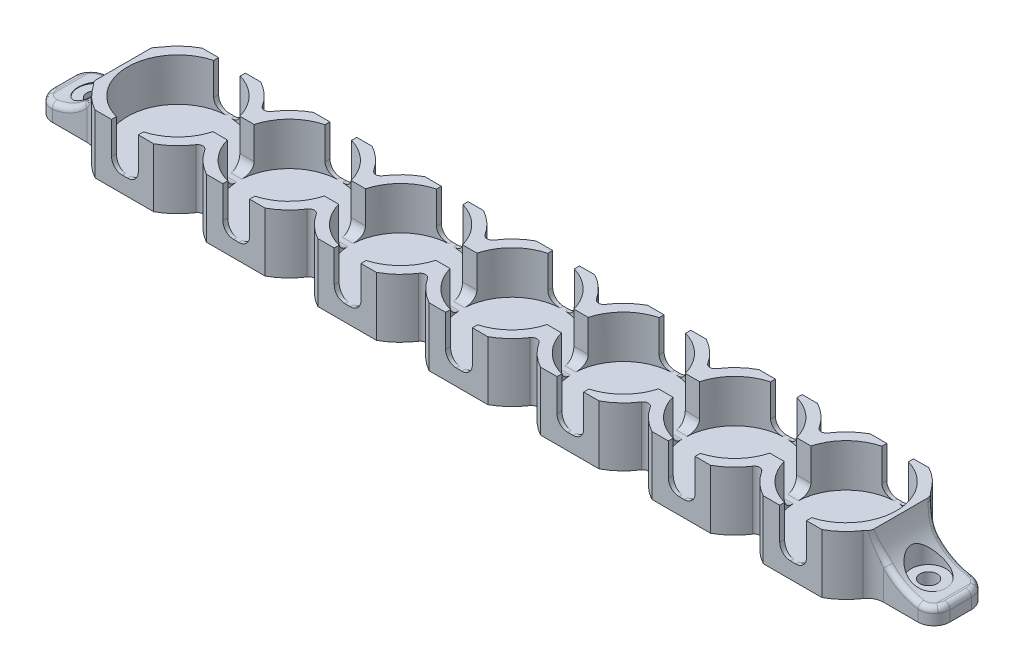
SolidWorks part; units mm, degrees
ref_plane "Front Plane" through (0, 0, 0) normal (0, 0, 1) x (1, 0, 0)
ref_plane "Top Plane" through (0, 0, 0) normal (0, 1, 0) x (1, 0, 0)
ref_plane "Right Plane" through (0, 0, 0) normal (1, 0, 0) x (0, 0, -1)
sketch "Sketch1" plane through (0, 0, 0) normal (0, 1, 0) x (1, 0, 0)
  line L0 (21.4, 5) -> (146.2, 5) construction
  line L1 (0, 10) -> (11.155, 10)
  line L2 (0, 0) -> (0, 10)
  line L3 (0, 0) -> (11.155, 0)
  line L4 (167.6, 0) -> (167.6, 10)
  line L5 (156.445, 10) -> (167.6, 10)
  line L6 (156.445, 0) -> (167.6, 0)
  line L7 (21.4, 5) -> (0, 5) construction
  line L8 (146.2, 5) -> (167.6, 5) construction
  circle A0 centre (21.4, 5) radius 9.4
  circle A1 centre (42.2, 5) radius 9.4
  circle A2 centre (63, 5) radius 9.4
  circle A3 centre (83.8, 5) radius 9.4
  circle A4 centre (104.6, 5) radius 9.4
  circle A5 centre (125.4, 5) radius 9.4
  circle A6 centre (146.2, 5) radius 9.4
  arc A7 (11.155, 10) -> (31.8, 9.669) centre (21.4, 5) cw
  arc A8 (31.8, 9.669) -> (52.6, 9.669) centre (42.2, 5) cw
  arc A9 (52.6, 9.669) -> (73.4, 9.669) centre (63, 5) cw
  arc A10 (73.4, 9.669) -> (94.2, 9.669) centre (83.8, 5) cw
  arc A11 (94.2, 9.669) -> (115, 9.669) centre (104.6, 5) cw
  arc A12 (115, 9.669) -> (135.8, 9.669) centre (125.4, 5) cw
  arc A13 (135.8, 9.669) -> (156.445, 10) centre (146.2, 5) cw
  arc A14 (11.155, 0) -> (31.8, 0.331) centre (21.4, 5) ccw
  arc A15 (31.8, 0.331) -> (52.6, 0.331) centre (42.2, 5) ccw
  arc A16 (52.6, 0.331) -> (73.4, 0.331) centre (63, 5) ccw
  arc A17 (73.4, 0.331) -> (94.2, 0.331) centre (83.8, 5) ccw
  arc A18 (94.2, 0.331) -> (115, 0.331) centre (104.6, 5) ccw
  arc A19 (115, 0.331) -> (135.8, 0.331) centre (125.4, 5) ccw
  arc A20 (135.8, 0.331) -> (156.445, 0) centre (146.2, 5) ccw
  dimension "D1" = 18.8
  dimension "D4" = 2
  dimension "D5" = 12
  dimension "D7" = 2
  dimension "D3" = 10
  dimension "D2" = 7
extrude "Boss-Extrude1" add sketch "Sketch1" along normal blind 11
sketch "Sketch2" plane through (0, 0, 0) normal (0, -1, 0) x (1, 0, 0)
  circle A0 centre (21.4, -5) radius 1.3526
  circle A1 centre (63, -5) radius 1.3525
  circle A2 centre (83.8, -5) radius 1.3525
  circle A3 centre (104.6, -5) radius 1.3525
  circle A4 centre (125.4, -5) radius 1.3526
  circle A5 centre (146.2, -5) radius 9.4 construction
  circle A6 centre (146.2, -5) radius 1.3526
  circle A7 centre (42.2, -5) radius 1.3526
  circle A8 centre (42.2, -5) radius 9.4 construction
  circle A9 centre (146.2, -5) radius 9.4
  circle A10 centre (125.4, -5) radius 9.4
  circle A11 centre (104.6, -5) radius 9.4
  circle A12 centre (83.8, -5) radius 9.4
  circle A13 centre (63, -5) radius 9.4
  circle A14 centre (21.4, -5) radius 9.4 construction
  circle A15 centre (63, -5) radius 9.4 construction
  circle A16 centre (83.8, -5) radius 9.4 construction
  circle A17 centre (104.6, -5) radius 9.4 construction
  circle A18 centre (125.4, -5) radius 9.4 construction
  circle A19 centre (42.2, -5) radius 9.4
  circle A20 centre (21.4, -5) radius 9.4
  dimension "D1" = 2.7051
extrude "Boss-Extrude3" add sketch "Sketch2" against normal blind 3
sketch "Sketch13" plane through (0, 0, 0) normal (0, 0, 1) x (1, 0, 0)
  line L0 (0, 11) -> (0, 0) construction
  line L1 (11.155, 11) -> (0, 11)
  line L2 (11.155, 11) -> (11.155, 3)
  line L4 (11.155, 3) -> (0, 3)
  line L5 (167.6, 11) -> (167.6, 0) construction
  line L6 (0, 11) -> (0, 3)
  line L7 (156.445, 11) -> (167.6, 11)
  line L8 (156.445, 11) -> (156.445, 3)
  line L9 (0, 0) -> (11.155, 0) construction
  line L10 (156.445, 3) -> (167.6, 3)
  line L11 (167.6, 11) -> (167.6, 3)
  line L12 (156.445, 0) -> (167.6, 0) construction
  dimension "D1" = 3
  dimension "D2" = 3
extrude "Cut-Extrude4" cut sketch "Sketch13" against normal through all both and the other way through all
fillet "Fillet2" radius 1 12 edges at (31.8, 5.5, -9.669) (52.6, 5.5, -9.669) (73.4, 5.5, -9.669) (94.2, 5.5, -9.669) (115, 5.5, -9.669) (135.8, 5.5, -9.669) (135.8, 5.5, -0.331) (115, 5.5, -0.331) (94.2, 5.5, -0.331) (73.4, 5.5, -0.331) (52.6, 5.5, -0.331) (31.8, 5.5, -0.331)
fillet "Fillet4" radius 10 2 edges at (11.155, 3, -5) (156.445, 3, -5)
fillet "Fillet5" radius 3 8 edges at (11.155, 5.5, 0) (0, 1.5, 0) (0, 1.5, -10) (11.155, 5.5, -10) (156.445, 5.5, 0) (156.445, 5.5, -10) (167.6, 1.5, 0) (167.6, 1.5, -10)
fillet "Fillet6" radius 1 18 edges at (156.9374, 9.3385, -10.2664) (160.9989, 4.4853, -10) (167.239, 3, -8.4267) (157.4781, 8.1858, 0.0817) (160.9989, 4.4853, 0) (167.239, 3, -1.5733) (10.6626, 9.3385, 0.2664) (6.6011, 4.4853, 0) (0.361, 3, -1.5733) (10.1219, 8.1858, -10.0817) (6.6011, 4.4853, -10) (0.361, 3, -8.4267) (167.6, 3, -5) (0, 3, -5) (165.3504, 3.0399, -9.9046) (165.5574, 3.0235, -0.1569) (2.2496, 3.0399, -0.0954) (2.0426, 3.0235, -9.8431)
sketch "Sketch14" plane through (0, 0, 0) normal (0, -1, 0) x (1, 0, 0)
  line L0 (0, -7) -> (0, -3) construction
  line L1 (6, -5) -> (0, -5) construction
  line L4 (161.6, -5) -> (167.6, -5) construction
  line L5 (167.6, -3) -> (167.6, -7) construction
  circle A0 centre (6, -5) radius 1.6
  circle A1 centre (161.6, -5) radius 1.6
  point P9 (167.6, -5)
  point P11 (0, -5)
  dimension "D1" = 3.2
  dimension "D2" = 6
extrude "Cut-Extrude5" cut sketch "Sketch14" against normal through all
sketch "Sketch16" plane through (0, 11, 0) normal (0, -1, 0) x (1, 0, 0)
  circle A1 centre (6, -5) radius 3.25
  circle A2 centre (161.6, -5) radius 3.25
  circle A3 centre (161.6, -5) radius 1.6 construction
  circle A4 centre (6, -5) radius 1.6 construction
  dimension "D1" = 6.5
extrude "Cut-Extrude7" cut sketch "Sketch16" along normal offset from surface (8 mm away) 3 up to face at (161.6, 0, -6.6)
sketch "Sketch17" plane through (0, 0, 0) normal (0, 0, 1) x (1, 0, 0)
  line L0 (30.8, 3) -> (12, 3) construction
  line L1 (19, 18) -> (24, 18)
  line L2 (19, 18) -> (19, 3)
  line L3 (19, 3) -> (24, 3)
  line L4 (24, 18) -> (24, 3)
  line L5 (39.8, 18) -> (44.8, 18)
  line L6 (39.8, 18) -> (39.8, 3)
  line L7 (39.8, 3) -> (44.8, 3)
  line L8 (44.8, 18) -> (44.8, 3)
  line L9 (60.6, 18) -> (65.6, 18)
  line L10 (60.6, 18) -> (60.6, 3)
  line L11 (60.6, 3) -> (65.6, 3)
  line L12 (65.6, 18) -> (65.6, 3)
  line L13 (81.4, 18) -> (86.4, 18)
  line L14 (81.4, 18) -> (81.4, 3)
  line L15 (81.4, 3) -> (86.4, 3)
  line L16 (86.4, 18) -> (86.4, 3)
  line L17 (102.2, 18) -> (107.2, 18)
  line L18 (102.2, 18) -> (102.2, 3)
  line L19 (102.2, 3) -> (107.2, 3)
  line L20 (107.2, 18) -> (107.2, 3)
  line L21 (123, 18) -> (128, 18)
  line L22 (123, 18) -> (123, 3)
  line L23 (123, 3) -> (128, 3)
  line L24 (128, 18) -> (128, 3)
  line L25 (143.8, 18) -> (148.8, 18)
  line L26 (143.8, 18) -> (143.8, 3)
  line L27 (143.8, 3) -> (148.8, 3)
  line L28 (148.8, 18) -> (148.8, 3)
  line L31 (155.6, 3) -> (136.8, 3) construction
  point P6 (21.5, 3)
  point P7 (42.3, 3)
  dimension "D1" = 21.5
  dimension "D2" = 5
  dimension "D3" = 15
  dimension "D5" = 20.8
  dimension "D4" = 7
extrude "Cut-Extrude8" cut sketch "Sketch17" against normal through all both and the other way through all
sketch "Sketch18" plane through (0, 0, 0) normal (1, 0, 0) x (0, 0, -1)
  line L0 (5, 3) -> (5, 0) construction
  line L1 (2.5, 18) -> (7.5, 18)
  line L2 (2.5, 18) -> (2.5, 3)
  line L3 (2.5, 3) -> (7.5, 3)
  line L4 (7.5, 18) -> (7.5, 3)
  line L5 (7, 0) -> (3, 0) construction
  line L6 (14.0885, 3) -> (-4.0885, 3) construction
  dimension "D1" = 5
  dimension "D2" = 15
extrude "Cut-Extrude9" cut sketch "Sketch18" along normal offset from surface (124.6 mm away) 21.5 from offset 21.5 up to face at (167.6, 1, -5)
fillet "Fillet7" radius 2 40 edges at (143.8, 3, -15.1165) (148.8, 3, -15.0664) (135.8, 3, -2.5) (135.8, 3, -7.5) (128, 3, -15.0664) (123, 3, -15.1165) (115, 3, -2.5) (115, 3, -7.5) (107.2, 3, -15.0664) (102.2, 3, -15.1165) (94.2, 3, -7.5) (94.2, 3, -2.5) (86.4, 3, -15.0664) (81.4, 3, -15.1165) (73.4, 3, -2.5) (73.4, 3, -7.5) (65.6, 3, -15.0664) (60.6, 3, -15.1165) (52.6, 3, -2.5) (52.6, 3, -7.5) (44.8, 3, -15.0664) (39.8, 3, -15.1165) (31.8, 3, -2.5) (31.8, 3, -7.5) (24, 3, -15.0664) (19, 3, -15.1165) (143.8, 3, 5.1165) (148.8, 3, 5.0664) (128, 3, 5.0664) (123, 3, 5.1165) (102.2, 3, 5.1165) (107.2, 3, 5.0664) (86.4, 3, 5.0664) (81.4, 3, 5.1165) (60.6, 3, 5.1165) (65.6, 3, 5.0664) (44.8, 3, 5.0664) (39.8, 3, 5.1165) (24, 3, 5.0664) (19, 3, 5.1165)
sketch "Sketch19" plane through (0, 0, 0) normal (0, 1, 0) x (1, 0, 0)
  line L0 (0, 7) -> (0, 3) construction
  line L3 (0, 15) -> (167.6, 15)
  line L4 (0, 15) -> (0, -5)
  line L5 (0, -5) -> (167.6, -5)
  line L6 (167.6, 15) -> (167.6, -5)
  line L7 (167.6, 3) -> (167.6, 7) construction
  point P4 (0, 5)
  point P7 (0, 5)
  dimension "D1" = 20
extrude "Cut-Extrude12" cut sketch "Sketch19" along normal through all flip side to cut
